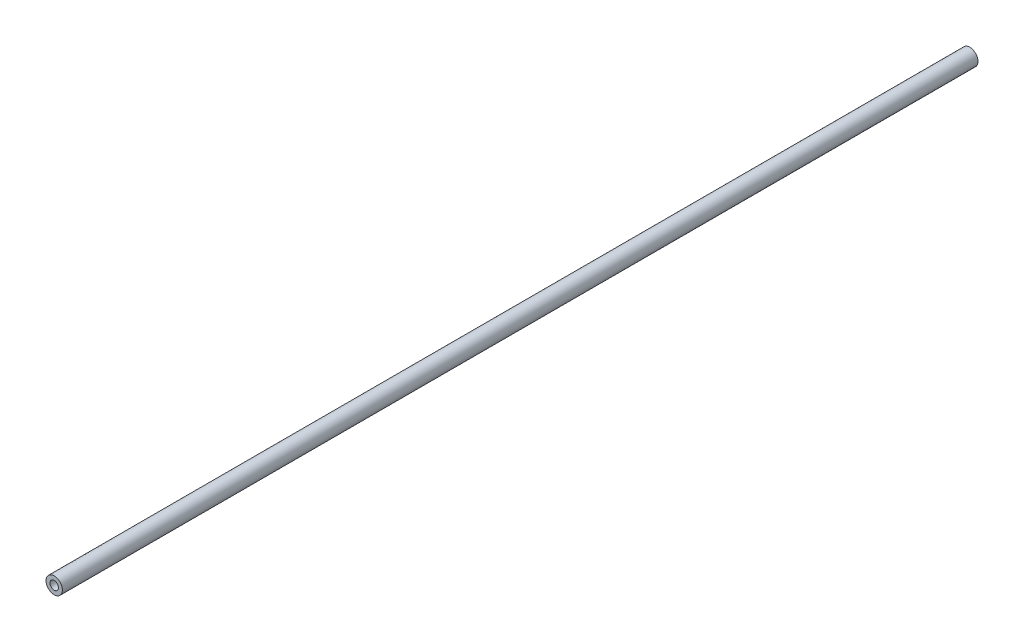
SolidWorks part; units mm, degrees
material "6061 Alloy"
ref_plane "Front Plane" through (0, 0, 0) normal (0, 0, 1) x (1, 0, 0)
ref_plane "Top Plane" through (0, 0, 0) normal (0, 1, 0) x (1, 0, 0)
ref_plane "Right Plane" through (0, 0, 0) normal (1, 0, 0) x (0, 0, -1)
sketch "Sketch1" plane through (0, 0, 0) normal (0, 0, 1) x (1, 0, 0)
  circle A0 centre (0, 0) radius 5
  dimension "D1" = 10
extrude "Boss-Extrude1" add sketch "Sketch1" along normal blind 559
hole_wizard "#6 (0.204) Diameter Hole1" positions "Sketch2" profile "Sketch3" hole size "#6" standard "ANSI Inch"
sketch "Sketch2" plane through (0, 0, 0) normal (0, 0, -1) x (-1, 0, 0)
  point P0 (0, 0)
sketch "Sketch3" plane through (0, 0, 0) normal (1, 0, 0) x (0, 1, 0)
  line L0 (0, 0) -> (0, 31.5567)
  line L1 (0, 31.5567) -> (2.5908, 30)
  line L2 (2.5908, 30) -> (2.5908, 0)
  line L5 (2.5908, 0) -> (0, 0)
  line L10 (0, 31.5567) -> (-2.5908, 30) construction
  line L11 (0, -6.35) -> (0, 107.95) construction
  dimension "Hole Dia." = 5.1816
  dimension "Hole Depth" = 30
  dimension "Drill Angle" = 118
hole_wizard "#6 (0.204) Diameter Hole2" positions "Sketch4" profile "Sketch5" hole size "#6" standard "ANSI Inch"
sketch "Sketch4" plane through (0, 0, 559) normal (0, 0, 1) x (1, 0, 0)
  point P0 (0, 0)
sketch "Sketch5" plane through (0, 0, 559) normal (1, 0, 0) x (0, -1, 0)
  line L0 (0, 0) -> (0, 31.5567)
  line L1 (0, 31.5567) -> (2.5908, 30)
  line L2 (2.5908, 30) -> (2.5908, 0)
  line L5 (2.5908, 0) -> (0, 0)
  line L10 (0, 31.5567) -> (-2.5908, 30) construction
  line L11 (0, -6.35) -> (0, 107.95) construction
  dimension "Hole Dia." = 5.1816
  dimension "Hole Depth" = 30
  dimension "Drill Angle" = 118
